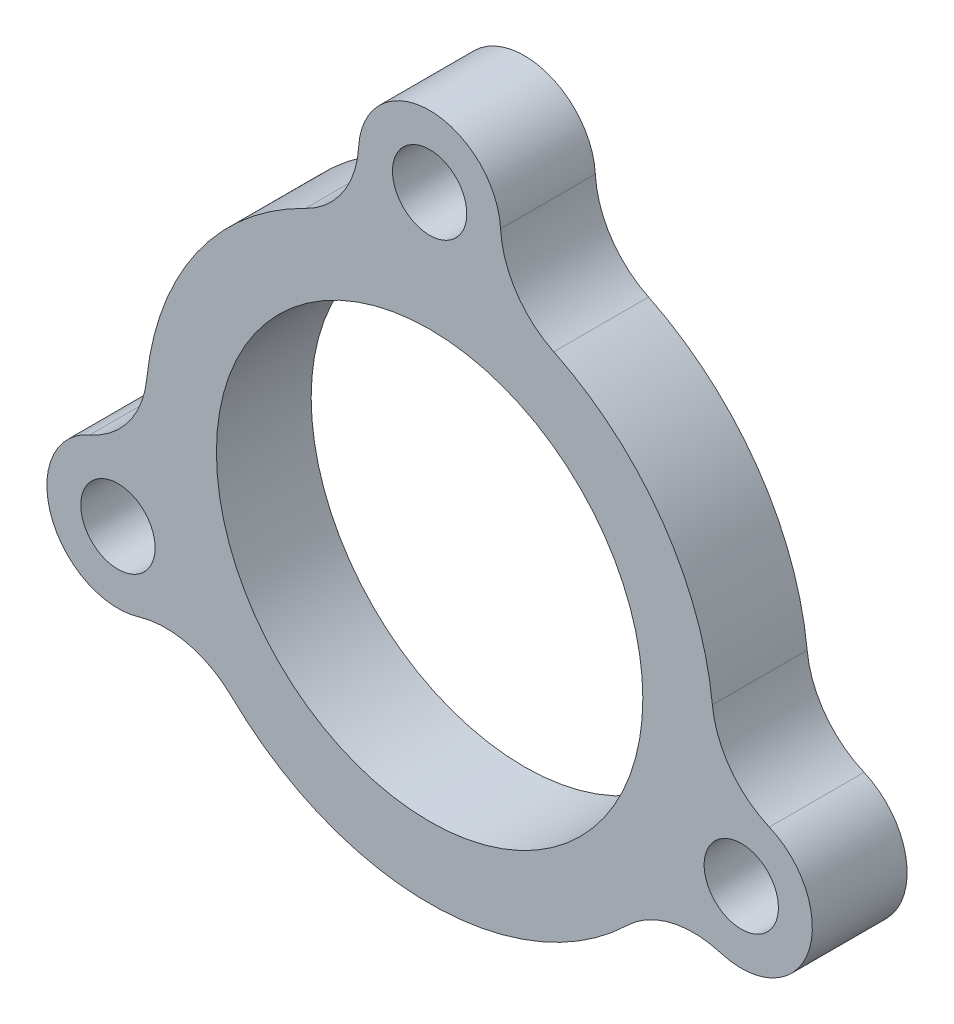
SolidWorks part; units mm, degrees
material "6061-T6 (SS)"
ref_plane "Front Plane" through (0, 0, 0) normal (0, 0, 1) x (1, 0, 0)
ref_plane "Top Plane" through (0, 0, 0) normal (0, 1, 0) x (1, 0, 0)
ref_plane "Right Plane" through (0, 0, 0) normal (1, 0, 0) x (0, 0, -1)
sketch "Sketch2" plane through (0, 0, 0) normal (0, 0, 1) x (1, 0, 0)
  line L0 (0, 0) -> (-20.8847, -7.6014) construction
  line L3 (0, 0) -> (20.8847, -7.6014) construction
  line L4 (0, 0) -> (0, 22.225) construction
  circle A0 centre (0, 0) radius 14.2875
  circle A1 centre (0, 22.225) radius 2.4892
  circle A2 centre (20.8847, -7.6014) radius 2.4892
  circle A3 centre (-20.8847, -7.6014) radius 2.4892
  circle A4 centre (20.8847, -7.6014) radius 4.7625
  circle A5 centre (0, 0) radius 19.05
  circle A6 centre (0, 22.225) radius 4.7625
  circle A7 centre (-20.8847, -7.6014) radius 4.7625
  point P11 (0, 0)
  dimension "D1" = 28.575
  dimension "D2" = 4.9784
  dimension "D6" = 9.525
  dimension "D5" = 38.1
  dimension "D3" = 22.225
  dimension "D4" = 110
  dimension "D7" = 110
extrude "Boss-Extrude1" add sketch "Sketch2" along normal blind 6.35 contours A7 A5 A4 A6 A0 | A5 A6 A1 | A5 A4 A2 | A5 A7 A3 | A5 A6 | A4 A5 | A5 A7 region at (21.825, -12.1355, 0) region at (17.2435, -6.2761, 0) region at (15.9049, -5.7889, 0) region at (-25.236, -9.1851, 0) region at (-17.2435, -6.2761, 0) region at (0, 18.3501, 0) region at (0, 19.1758, 0)
fillet "Fillet2" radius 6.35 6 edges at (-18.7546, -3.3418, 3.175) (-3.2742, 18.7665, 3.175) (18.7546, -3.3418, 3.175) (16.5149, -9.4953, 3.175) (-16.5149, -9.4953, 3.175) (3.2742, 18.7665, 3.175)
equation "\"D7@Sketch2\"=\"D4@Sketch2\""
